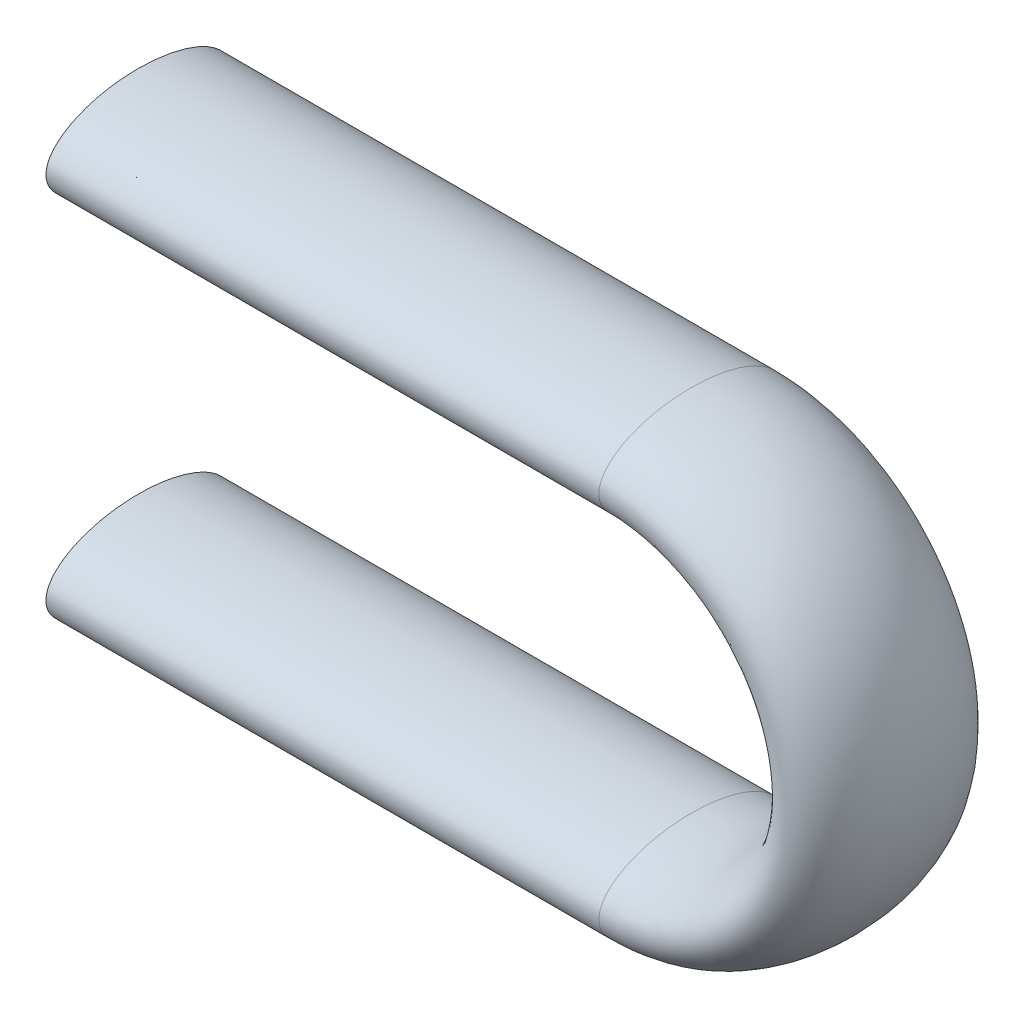
SolidWorks part; units mm, degrees
ref_plane "Front Plane" through (0, 0, 0) normal (0, 0, 1) x (1, 0, 0)
ref_plane "Top Plane" through (0, 0, 0) normal (0, 1, 0) x (1, 0, 0)
ref_plane "Right Plane" through (0, 0, 0) normal (1, 0, 0) x (0, 0, -1)
sketch "Sketch1" plane through (0, 0, 0) normal (0, 0, 1) x (1, 0, 0)
  line L0 (0, 0) -> (304.8, 0)
  line L1 (0, 203.2) -> (304.8, 203.2)
  line L2 (406.4, 101.6) -> (0, 101.6) construction
  arc A0 (304.8, 203.2) -> (304.8, 0) centre (304.8, 101.6) cw
  point P6 (0, 0)
  dimension "D2" = 101.6
  dimension "D1" = 304.8
sketch "Sketch2" plane through (0, 0, 0) normal (1, 0, 0) x (0, 0, -1)
  line L0 (-50.8, 0) -> (50.8, 0) construction
  ellipse E0 centre (0, 0) end of major axis (50.8, 0) minor radius 25.4
  dimension "D1" = 101.6
  dimension "D2" = 50.8
sweep "Sweep1" add profiles "Sketch2" path "Sketch1"
sketch "Sketch3" plane through (0, 0, 0) normal (-1, 0, 0) x (0, 0, 1)
  circle A0 centre (0, 0) radius 19.05
  dimension "D1" = 38.1
sweep "Cut-Sweep1" cut profiles "Sketch3" path "Sketch1<3>"
sketch "Sketch1<3>" plane through (0, 0, 0) normal (0, 0, 1) x (1, 0, 0) same geometry as "Sketch1"
